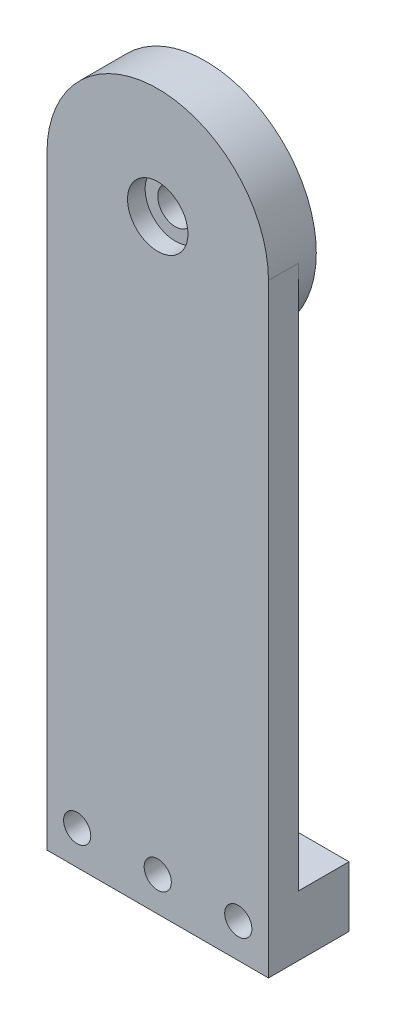
SolidWorks part; units mm, degrees
ref_plane "Front Plane" through (0, 0, 0) normal (0, 0, 1) x (1, 0, 0)
ref_plane "Top Plane" through (0, 0, 0) normal (0, 1, 0) x (1, 0, 0)
ref_plane "Right Plane" through (0, 0, 0) normal (1, 0, 0) x (0, 0, -1)
sketch "Sketch1" plane through (0, 0, 0) normal (0, 0, 1) x (1, 0, 0)
  line L0 (0, 30) -> (0, -30) construction
  line L1 (-11, 30) -> (-11, -30)
  line L2 (11, 30) -> (11, -30)
  line L3 (-11, -30) -> (11, -30)
  line L5 (-11, -30) -> (11, -30)
  line L6 (-11, -30) -> (-11, -24)
  line L7 (-11, -24) -> (11, -24)
  line L8 (11, -30) -> (11, -24)
  circle A0 centre (0, 30) radius 11
  point P8 (0, 0)
  dimension "D2" = 22
  dimension "D1" = 60
  dimension "D3" = 6
extrude "Boss-Extrude1" add sketch "Sketch1" along normal blind 3 contours A0 | L0 A0 L1 | A0 L0 L2 | L6 L5 L8 L7 region at (0, -1.2532, 0) region at (0, 30, 0)
extrude "Boss-Extrude2" add sketch "Sketch1<3>" against normal blind 1.75 contours A0 region at (0, 30, 0)
sketch "Sketch1<3>" plane through (0, 0, 0) normal (0, 0, 1) x (1, 0, 0) same geometry as "Sketch1"
sketch "Sketch2" plane through (0, 0, 3) normal (0, 0, 1) x (1, 0, 0)
  circle A0 centre (0, 30) radius 1.75
  circle A3 centre (0, 30) radius 3
  dimension "D1" = 3.5
  dimension "D2" = 6
extrude "Cut-Extrude1" cut sketch "Sketch2" against normal up to surface (4.75 mm away) contours A0 region at (0, 30, 3) up to face at (11, 30, -1.75)
extrude "Cut-Extrude2" cut sketch "Sketch2<3>" against normal offset from surface (1.75 mm away) 3 contours A3 A0 region at (-2.9151, 30, 3) up to face at (1.75, 30, -1.75)
sketch "Sketch2<3>" plane through (0, 0, 3) normal (0, 0, 1) x (1, 0, 0) same geometry as "Sketch2"
extrude "Boss-Extrude3" add sketch "Sketch1<6>" against normal blind 5 contours L7 L0 L5 L2 | L0 L7 L1 L3 region at (5.5, -27, 0) region at (-5.5, -27, 0)
sketch "Sketch1<6>" plane through (0, 0, 0) normal (0, 0, 1) x (1, 0, 0) same geometry as "Sketch1"
sketch "Sketch3" plane through (0, 0, 3) normal (0, 0, 1) x (1, 0, 0)
  line L0 (-11, -30) -> (11, -30) construction
  circle A0 centre (0, -26.6) radius 1.35
  dimension "D2" = 2.7
  dimension "D1" = 3.4
extrude "Cut-Extrude3" cut sketch "Sketch3" against normal up to surface (8 mm away) up to face at (0, -27, -5)
pattern_linear "LPattern1" count 2 spacing 8 along (1, 0, 0) count 2 spacing 8 along (-1, 0, 0) of "Cut-Extrude3"
